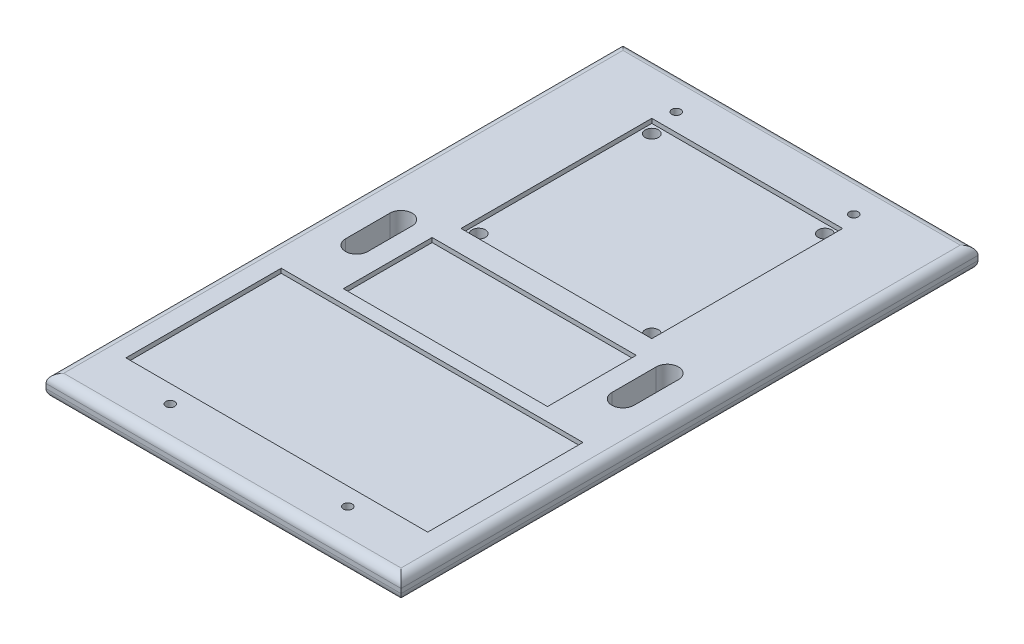
SolidWorks part; units mm, degrees
ref_plane "Front Plane" through (0, 0, 0) normal (0, 0, 1) x (1, 0, 0)
ref_plane "Top Plane" through (0, 0, 0) normal (0, 1, 0) x (1, 0, 0)
ref_plane "Right Plane" through (0, 0, 0) normal (1, 0, 0) x (0, 0, -1)
sketch "Sketch2" plane through (0, 0, 0) normal (0, 1, 0) x (1, 0, 0)
  line L0 (-40, 130) -> (-40, 0) construction
  line L1 (0, 0) -> (-80, 0)
  line L2 (0, 0) -> (0, 130)
  line L3 (0, 130) -> (-80, 130)
  line L4 (-80, 0) -> (-80, 130)
  line L5 (0, 65) -> (-80, 65) construction
  line L6 (-8, 28) -> (-8, 8) construction
  line L7 (-4, 28) -> (-4, 8)
  line L8 (-12, 28) -> (-12, 8)
  line L9 (-8, 102) -> (-8, 122) construction
  line L10 (-4, 102) -> (-4, 122)
  line L11 (-12, 102) -> (-12, 122)
  line L12 (-72, 102) -> (-72, 122) construction
  line L13 (-76, 102) -> (-76, 122)
  line L14 (-68, 102) -> (-68, 122)
  line L15 (-72, 28) -> (-72, 8) construction
  line L16 (-76, 28) -> (-76, 8)
  line L17 (-68, 28) -> (-68, 8)
  arc A0 (-4, 28) -> (-12, 28) centre (-8, 28) ccw
  arc A1 (-12, 8) -> (-4, 8) centre (-8, 8) ccw
  arc A2 (-4, 102) -> (-12, 102) centre (-8, 102) cw
  arc A3 (-12, 122) -> (-4, 122) centre (-8, 122) cw
  arc A4 (-76, 102) -> (-68, 102) centre (-72, 102) ccw
  arc A5 (-68, 122) -> (-76, 122) centre (-72, 122) ccw
  arc A6 (-76, 28) -> (-68, 28) centre (-72, 28) cw
  arc A7 (-68, 8) -> (-76, 8) centre (-72, 8) cw
  point P11 (-8, 18)
  point P16 (-4, 18)
  point P20 (-8, 112)
  point P27 (-72, 112)
  point P34 (-72, 18)
  dimension "D5" = 4
  dimension "D1" = 80
  dimension "D2" = 130
  dimension "D3" = 20
  dimension "D4" = 8
  dimension "D6" = 8
  dimension "D7" = 8
extrude "Boss-Extrude1" add sketch "Sketch2" against normal blind 3
sketch "Sketch3" plane through (0, 0, 0) normal (0, 1, 0) x (1, 0, 0)
  line L1 (-80, 0) -> (0, 0)
  line L2 (-80, 0) -> (-80, 130)
  line L3 (-80, 130) -> (0, 130)
  line L4 (0, 0) -> (0, 130)
extrude "Boss-Extrude2" add sketch "Sketch3" along normal blind 2
fillet "Fillet1" radius 2 8 edges at (-40, -3, -130) (-40, 2, -130) (-80, -3, -65) (-80, 2, -65) (0, 2, -65) (0, -3, -65) (-40, -3, 0) (-40, 2, 0)
sketch "Sketch4" plane through (0, 0, 0) normal (0, 1, 0) x (1, 0, 0)
  line L0 (-80, 65) -> (-2, 65) construction
  line L1 (-80, 130) -> (0, 130)
  line L2 (-80, 130) -> (-80, 0)
  line L3 (-80, 0) -> (0, 0)
  line L4 (0, 130) -> (0, 0)
  line L5 (0, 0) -> (-80, 0)
  line L6 (0, 0) -> (0, 130)
  line L7 (0, 130) -> (-80, 130)
  line L8 (-80, 0) -> (-80, 130)
  line L9 (-2, 2) -> (-2, 128) construction
  line L10 (-40, 130) -> (-40, 2) construction
  line L11 (-78, 2) -> (-2, 2) construction
  line L12 (-10, 70) -> (-10, 60) construction
  line L13 (-7.5, 70) -> (-7.5, 60)
  line L14 (-12.5, 70) -> (-12.5, 60)
  line L15 (-70, 70) -> (-70, 60) construction
  line L16 (-72.5, 70) -> (-72.5, 60)
  line L17 (-67.5, 70) -> (-67.5, 60)
  arc A0 (-7.5, 70) -> (-12.5, 70) centre (-10, 70) ccw
  arc A1 (-12.5, 60) -> (-7.5, 60) centre (-10, 60) ccw
  arc A2 (-72.5, 70) -> (-67.5, 70) centre (-70, 70) cw
  arc A3 (-67.5, 60) -> (-72.5, 60) centre (-70, 60) cw
  point P16 (-10, 65)
  point P25 (-70, 65)
  dimension "D1" = 10
  dimension "D2" = 5
  dimension "D3" = 8
extrude "Cut-Extrude1" cut sketch "Sketch4" against normal through all both and the other way through all contours L16 A3 L17 A2 | L14 A1 L13 A0
sketch "Sketch6" plane through (0, 2, 0) normal (0, 1, 0) x (1, 0, 0)
  line L0 (-40, 2) -> (-40, 128) construction
  line L1 (-78, 2) -> (-2, 2) construction
  line L2 (-2, 128) -> (-78, 128) construction
  line L3 (-78, 65) -> (-2, 65) construction
  line L4 (-78, 128) -> (-78, 2) construction
  line L5 (-2, 2) -> (-2, 128) construction
  line L6 (-61.5, 96.5) -> (-18.5, 96.5) construction
  line L7 (-78, 128) -> (-2, 128)
  line L8 (-78, 128) -> (-78, 2) construction
  line L9 (-78, 2) -> (-2, 2)
  line L10 (-2, 128) -> (-2, 2)
  line L11 (-6, 47) -> (-74, 47)
  line L12 (-6, 47) -> (-6, 12)
  line L13 (-6, 12) -> (-74, 12)
  line L14 (-74, 47) -> (-74, 12)
  line L15 (-6, 47) -> (-74, 12) construction
  line L16 (-6, 12) -> (-74, 47) construction
  line L17 (-18.5, 118) -> (-61.5, 118)
  line L18 (-18.5, 118) -> (-18.5, 75)
  line L19 (-18.5, 75) -> (-61.5, 75)
  line L20 (-61.5, 118) -> (-61.5, 75)
  line L21 (-18.5, 118) -> (-61.5, 75) construction
  line L22 (-18.5, 75) -> (-61.5, 118) construction
  line L23 (-17, 70) -> (-63, 70)
  line L24 (-17, 70) -> (-17, 50)
  line L25 (-17, 50) -> (-63, 50)
  line L26 (-63, 70) -> (-63, 50)
  line L27 (-17, 70) -> (-63, 50) construction
  line L28 (-17, 50) -> (-63, 70) construction
  line L29 (-40, 118) -> (-40, 75) construction
  circle A0 centre (-60, 122) radius 1
  circle A1 centre (-20, 122) radius 1
  circle A2 centre (-20, 8) radius 1
  circle A3 centre (-60, 8) radius 1
  circle A4 centre (-20.5, 116) radius 1.5
  circle A5 centre (-20.5, 77) radius 1.5
  circle A6 centre (-59.5, 77) radius 1.5
  circle A7 centre (-59.5, 116) radius 1.5
  point P26 (-40, 29.5)
  point P31 (-40, 96.5)
  point P36 (-40, 75)
  point P37 (-40, 60)
  dimension "D1" = 18
  dimension "D3" = 2
  dimension "D13" = 3
  dimension "D2" = 6
  dimension "D4" = 68
  dimension "D5" = 35
  dimension "D6" = 10
  dimension "D7" = 43
  dimension "D8" = 43
  dimension "D9" = 10
  dimension "D10" = 46
  dimension "D11" = 20
  dimension "D12" = 5
  dimension "D14" = 2
  dimension "D15" = 2
extrude "Cut-Extrude2" cut sketch "Sketch6" against normal blind 3 contours A3 | A2 | A1 | A0
extrude "Cut-Extrude3" cut sketch "Sketch6<3>" against normal blind 1 contours L11 L14 L13 L12 | L23 L26 L25 L24 | L17 L20 L19 L18 region at (-40, 2, -29.5) region at (-40, 2, -96.5) region at (-40, 2, -60)
sketch "Sketch6<3>" plane through (0, 2, 0) normal (0, 1, 0) x (1, 0, 0) same geometry as "Sketch6"
extrude "AgujerosL298N" cut sketch "Sketch6<4>" against normal through all contours A4 | A6 | A5 | A7 region at (-20.5, 2, -116) region at (-20.5, 2, -77) region at (-59.5, 2, -77)
sketch "Sketch6<4>" plane through (0, 2, 0) normal (0, 1, 0) x (1, 0, 0) same geometry as "Sketch6"
